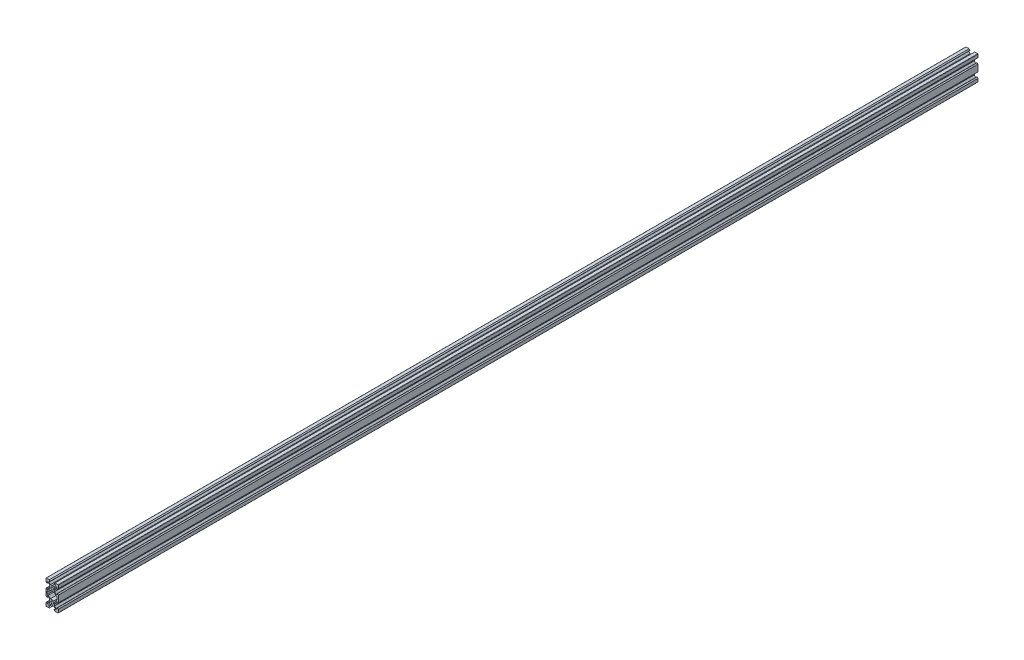
SolidWorks part; units mm, degrees
material "6061-T6 (SS)"
ref_plane "Front Plane" through (0, 0, 0) normal (0, 0, 1) x (1, 0, 0)
ref_plane "Top Plane" through (0, 0, 0) normal (0, 1, 0) x (1, 0, 0)
ref_plane "Right Plane" through (0, 0, 0) normal (1, 0, 0) x (0, 0, -1)
sketch "Sketch1" plane through (0, 0, 0) normal (0, 0, 1) x (1, 0, 0)
  line L0 (0, 0) -> (10, 0) construction
  line L1 (9.5, -20) -> (-9.5, -20)
  line L2 (10, -19.5) -> (10, 19.5)
  line L3 (9.5, 20) -> (-9.5, 20)
  line L4 (-10, -19.5) -> (-10, 19.5)
  line L5 (10, -20) -> (-10, 20) construction
  line L6 (10, 20) -> (-10, -20) construction
  circle A0 centre (0, 10) radius 2.1
  circle A1 centre (0, -10) radius 2.1
  arc A2 (-9.5, -20) -> (-10, -19.5) centre (-9.5, -19.5) cw
  arc A3 (9.5, -20) -> (10, -19.5) centre (9.5, -19.5) ccw
  arc A4 (10, 19.5) -> (9.5, 20) centre (9.5, 19.5) ccw
  arc A5 (-9.5, 20) -> (-10, 19.5) centre (-9.5, 19.5) ccw
  point P0 (0, 0)
  line B0 (0, 10) -> (0, 20) construction
  line B1 (0, 13.69) -> (-0.21, 13.9)
  line B2 (-0.21, 13.9) -> (-2.8393, 13.9)
  line B3 (-2.8393, 13.9) -> (-5.5, 16.5607)
  line B4 (-5.5, 16.5607) -> (-5.5, 18.2)
  line B5 (-5.5, 18.2) -> (-3.125, 18.2)
  line B6 (-3.125, 18.2) -> (-3.125, 18.545)
  line B7 (-3.125, 18.545) -> (-4.58, 20)
  line B8 (-4.58, 20) -> (4.58, 20)
  line B9 (0, 10) -> (-5.9132, 15.9132) construction
  line B10 (3.125, 18.545) -> (4.58, 20)
  line B11 (3.125, 18.2) -> (3.125, 18.545)
  line B12 (5.5, 18.2) -> (3.125, 18.2)
  line B13 (5.5, 16.5607) -> (5.5, 18.2)
  line B14 (2.8393, 13.9) -> (5.5, 16.5607)
  line B15 (0.21, 13.9) -> (2.8393, 13.9)
  line B16 (0, 13.69) -> (0.21, 13.9)
  line B17 (0, 10) -> (-10, 10) construction
  line B18 (-3.69, 10) -> (-3.9, 9.79)
  line B19 (-3.9, 9.79) -> (-3.9, 7.1607)
  line B20 (-3.9, 7.1607) -> (-6.5607, 4.5)
  line B21 (-6.5607, 4.5) -> (-8.2, 4.5)
  line B22 (-8.2, 4.5) -> (-8.2, 6.875)
  line B23 (-8.2, 6.875) -> (-8.545, 6.875)
  line B24 (-8.545, 6.875) -> (-10, 5.42)
  line B25 (-10, 5.42) -> (-10, 14.58)
  line B26 (0, 10) -> (-5.9132, 4.0868) construction
  line B27 (-8.545, 13.125) -> (-10, 14.58)
  line B28 (-8.2, 13.125) -> (-8.545, 13.125)
  line B29 (-8.2, 15.5) -> (-8.2, 13.125)
  line B30 (-6.5607, 15.5) -> (-8.2, 15.5)
  line B31 (-3.9, 12.8393) -> (-6.5607, 15.5)
  line B32 (-3.9, 10.21) -> (-3.9, 12.8393)
  line B33 (-3.69, 10) -> (-3.9, 10.21)
  line B34 (0, -10) -> (-10, -10) construction
  line B35 (-3.69, -10) -> (-3.9, -10.21)
  line B36 (-3.9, -10.21) -> (-3.9, -12.8393)
  line B37 (-3.9, -12.8393) -> (-6.5607, -15.5)
  line B38 (-6.5607, -15.5) -> (-8.2, -15.5)
  line B39 (-8.2, -15.5) -> (-8.2, -13.125)
  line B40 (-8.2, -13.125) -> (-8.545, -13.125)
  line B41 (-8.545, -13.125) -> (-10, -14.58)
  line B42 (-10, -14.58) -> (-10, -5.42)
  line B43 (0, -10) -> (-5.9132, -15.9132) construction
  line B44 (-8.545, -6.875) -> (-10, -5.42)
  line B45 (-8.2, -6.875) -> (-8.545, -6.875)
  line B46 (-8.2, -4.5) -> (-8.2, -6.875)
  line B47 (-6.5607, -4.5) -> (-8.2, -4.5)
  line B48 (-3.9, -7.1607) -> (-6.5607, -4.5)
  line B49 (-3.9, -9.79) -> (-3.9, -7.1607)
  line B50 (-3.69, -10) -> (-3.9, -9.79)
  line B51 (0, -10) -> (0, -20) construction
  line B52 (0, -13.69) -> (0.21, -13.9)
  line B53 (0.21, -13.9) -> (2.8393, -13.9)
  line B54 (2.8393, -13.9) -> (5.5, -16.5607)
  line B55 (5.5, -16.5607) -> (5.5, -18.2)
  line B56 (5.5, -18.2) -> (3.125, -18.2)
  line B57 (3.125, -18.2) -> (3.125, -18.545)
  line B58 (3.125, -18.545) -> (4.58, -20)
  line B59 (4.58, -20) -> (-4.58, -20)
  line B60 (0, -10) -> (5.9132, -15.9132) construction
  line B61 (-3.125, -18.545) -> (-4.58, -20)
  line B62 (-3.125, -18.2) -> (-3.125, -18.545)
  line B63 (-5.5, -18.2) -> (-3.125, -18.2)
  line B64 (-5.5, -16.5607) -> (-5.5, -18.2)
  line B65 (-2.8393, -13.9) -> (-5.5, -16.5607)
  line B66 (-0.21, -13.9) -> (-2.8393, -13.9)
  line B67 (0, -13.69) -> (-0.21, -13.9)
  line B68 (0, -10) -> (10, -10) construction
  line B69 (3.69, -10) -> (3.9, -9.79)
  line B70 (3.9, -9.79) -> (3.9, -7.1607)
  line B71 (3.9, -7.1607) -> (6.5607, -4.5)
  line B72 (6.5607, -4.5) -> (8.2, -4.5)
  line B73 (8.2, -4.5) -> (8.2, -6.875)
  line B74 (8.2, -6.875) -> (8.545, -6.875)
  line B75 (8.545, -6.875) -> (10, -5.42)
  line B76 (10, -5.42) -> (10, -14.58)
  line B77 (0, -10) -> (5.9132, -4.0868) construction
  line B78 (8.545, -13.125) -> (10, -14.58)
  line B79 (8.2, -13.125) -> (8.545, -13.125)
  line B80 (8.2, -15.5) -> (8.2, -13.125)
  line B81 (6.5607, -15.5) -> (8.2, -15.5)
  line B82 (3.9, -12.8393) -> (6.5607, -15.5)
  line B83 (3.9, -10.21) -> (3.9, -12.8393)
  line B84 (3.69, -10) -> (3.9, -10.21)
  line B85 (0, 10) -> (10, 10) construction
  line B86 (3.69, 10) -> (3.9, 10.21)
  line B87 (3.9, 10.21) -> (3.9, 12.8393)
  line B88 (3.9, 12.8393) -> (6.5607, 15.5)
  line B89 (6.5607, 15.5) -> (8.2, 15.5)
  line B90 (8.2, 15.5) -> (8.2, 13.125)
  line B91 (8.2, 13.125) -> (8.545, 13.125)
  line B92 (8.545, 13.125) -> (10, 14.58)
  line B93 (10, 14.58) -> (10, 5.42)
  line B94 (0, 10) -> (5.9132, 15.9132) construction
  line B95 (8.545, 6.875) -> (10, 5.42)
  line B96 (8.2, 6.875) -> (8.545, 6.875)
  line B97 (8.2, 4.5) -> (8.2, 6.875)
  line B98 (6.5607, 4.5) -> (8.2, 4.5)
  line B99 (3.9, 7.1607) -> (6.5607, 4.5)
  line B100 (3.9, 9.79) -> (3.9, 7.1607)
  line B101 (3.69, 10) -> (3.9, 9.79)
  line B102 (-8.2, -2.7) -> (-8.2, 2.7)
  line B103 (-8.2, 2.7) -> (-6.2393, 2.7)
  line B104 (-6.2393, 2.7) -> (-2.8393, 6.1)
  line B105 (-2.8393, 6.1) -> (2.8393, 6.1)
  line B106 (0, 6.1) -> (0, 0) construction
  line B107 (0, 0) -> (-8.2, 0) construction
  line B108 (6.2393, 2.7) -> (2.8393, 6.1)
  line B109 (8.2, 2.7) -> (6.2393, 2.7)
  line B110 (8.2, -2.7) -> (8.2, 2.7)
  line B111 (8.2, -2.7) -> (6.2393, -2.7)
  line B112 (6.2393, -2.7) -> (2.8393, -6.1)
  line B113 (-2.8393, -6.1) -> (2.8393, -6.1)
  line B114 (-6.2393, -2.7) -> (-2.8393, -6.1)
  line B115 (-8.2, -2.7) -> (-6.2393, -2.7)
  line B116 (0, 6.1) -> (0, 10) construction
  line B117 (0, 10) -> (-5.0927, 4.9073) construction
  dimension "D4" = 4.2
  dimension "D5" = 0.5
  dimension "D1" = 20
  dimension "D2" = 40
  dimension "D3" = 20
sketch_block_instance "V Slot 1-4"
sketch_block "V Slot 1" parameters "D1"=10, "D2"=11, "D3"=4.3, "D4"=1.8, "D5"=0.21, "D6"=45, "D7"=9.16, "D8"=1.5, "D9"=6.25
sketch_block_instance "V Slot 1-5"
sketch_block_instance "V Slot 1-6"
sketch_block_instance "V Slot 1-7"
sketch_block_instance "V Slot 1-8"
sketch_block_instance "V Slot 1-9"
sketch_block_instance "Center Cutout 1-1"
sketch_block "Center Cutout 1" parameters "D1"=5.4, "D2"=12.2, "D3"=8.2, "D4"=45, "D5"=10, "D6"=1.5
extrude "Boss-Extrude1" add sketch "Sketch1" along normal blind 1500 contours B101 B86 B87 B88 B89 B90 B91 B92 L2 A4 L3 B10 B11 B12 B13 B14 B15 B16 B1 B2 B3 B4 B5 B6 B7 A5 L4 B27 B28 B29 B30 B31 B32 B33 B18 B19 B20 B21 B22 B23 B24 B44 B45 B46 B47 B48 B49 B50 B35 region at (7.04, -19.5528, 0)
